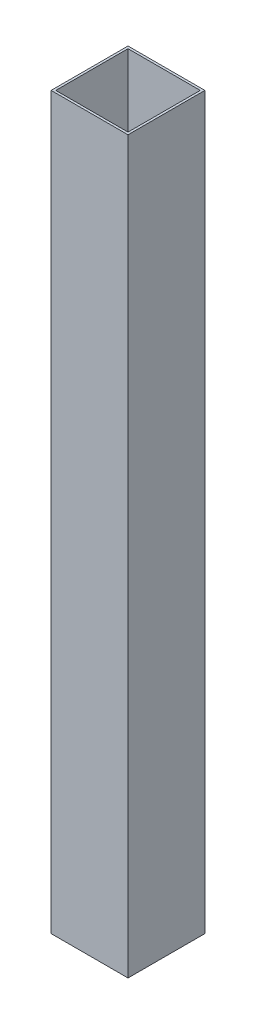
SolidWorks part; units mm, degrees
material "6061 Alloy"
ref_plane "Front Plane" through (0, 0, 0) normal (0, 0, 1) x (1, 0, 0)
ref_plane "Top Plane" through (0, 0, 0) normal (0, 1, 0) x (1, 0, 0)
ref_plane "Right Plane" through (0, 0, 0) normal (1, 0, 0) x (0, 0, -1)
sketch "Sketch1" plane through (0, 0, 0) normal (0, 1, 0) x (1, 0, 0)
  line L1 (25.4, 25.4) -> (-25.4, 25.4)
  line L2 (25.4, 25.4) -> (25.4, -25.4)
  line L3 (25.4, -25.4) -> (-25.4, -25.4)
  line L4 (-25.4, 25.4) -> (-25.4, -25.4)
  line L5 (25.4, 25.4) -> (-25.4, -25.4) construction
  line L6 (25.4, -25.4) -> (-25.4, 25.4) construction
  point P0 (0, 0)
  dimension "D1" = 50.8
extrude "Extrude-Thin1" add sketch "Sketch1" along normal blind 482.6 thin thin type one direction reverse wall 1.524
